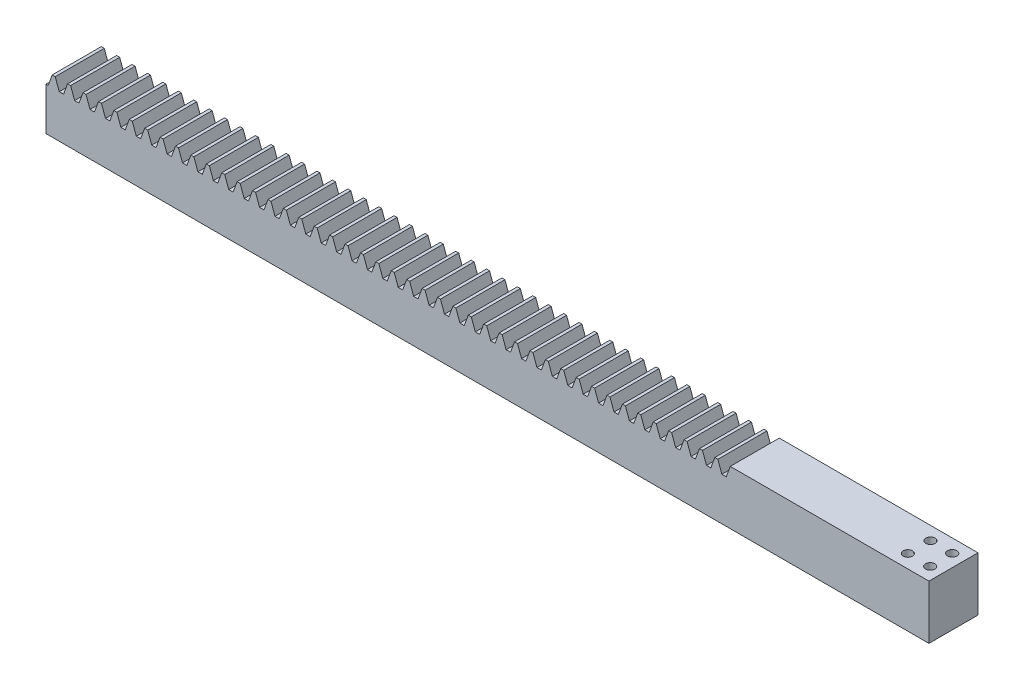
SolidWorks part; units mm, degrees
extrude "Blank" add sketch "BlankSke" against normal blind 10
sketch "BlankSke" plane through (0, 0, 0) normal (0, 0, 1) x (1, 0, 0)
  line L1 (0, 0) -> (140, 0)
  line L2 (0, 0) -> (0, 11)
  line L3 (0, 11) -> (140, 11)
  line L4 (140, 0) -> (140, 11)
  dimension "Length" = 140
ref_plane "Plane1" through (0, 0, 0) normal (0, 0, 1) x (1, 0, 0)
ref_plane "Plane2" through (0, 0, 0) normal (0, 1, 0) x (1, 0, 0)
ref_plane "Plane3" through (0, 0, 0) normal (1, 0, 0) x (0, 0, -1)
other "Configuration Table"
sketch "HoldingSke" plane through (0, 0, 0) normal (0, 1, 0) x (1, 0, 0)
  line L0 (0, 0) -> (0.1392, 0.9903)
  line L1 (-15, 0) -> (100, 0) construction
  line L2 (0, 0) -> (-2.1039, 2.3779)
  line L3 (0, 0) -> (-11.863, 4.5341)
  line L4 (0, 0) -> (5.9991, 6.2122)
  line L5 (0, 0) -> (-23.7986, -8.8762)
  line L6 (0, 0) -> (-10.5278, -7.1032)
  line L9 (-71.009, 38.7566) -> (60.548, 86.6394)
  line L10 (-76.2, 3.3779) -> (-66.2, 3.3779)
  line L11 (0, 0) -> (-10, 0)
  line L12 (-76.2, 101.6) -> (-76.162, 101.6)
  line L13 (24.9733, 27.94) -> (52.9518, 28.4284)
  line L14 (24.9733, 27.94) -> (24.9743, 27.94)
  line L15 (24.9733, 27.94) -> (100.4006, 29.5858)
  circle A0 centre (0, 0) radius 19.05
  circle A1 centre (0, 0) radius 5
  circle A2 centre (0, 0) radius 12.7
  dimension "Num_teeth" = 46
  dimension "Width" = 10
  dimension "Length" = 140
  dimension "Pitch_height" = 10
sketch "TooCutSkeIll" plane through (0, 0, 0) normal (0, 0, 1) x (1, 0, 0)
  line L0 (-1.2538, 10.9737) -> (-0.5045, 8.9152)
  line L1 (-0.2687, 8.75) -> (0.2687, 8.75)
  line L2 (0.5045, 8.9152) -> (1.2538, 10.9737)
  line L3 (140, 11) -> (0, 11) construction
  line L4 (0, 0) -> (0, 64.897) construction
  line L5 (-13.208, 10) -> (12.954, 10) construction
  line L6 (0, 0) -> (140, 0) construction
  line L7 (0.8994, 10) -> (0.8994, 48.7463) construction
  line L8 (-0.8994, 10) -> (-0.8994, 48.7463) construction
  line L9 (1.2914, 11) -> (1.2914, 11.0254)
  line L10 (-1.2914, 11) -> (-1.2914, 11.0254)
  line L11 (-1.2914, 11.0254) -> (1.2914, 11.0254)
  arc A0 (0.2687, 8.75) -> (0.5045, 8.9152) centre (0.2687, 9.001) ccw
  arc A1 (-0.5045, 8.9152) -> (-0.2687, 8.75) centre (-0.2687, 9.001) ccw
  arc A2 (1.2914, 11) -> (1.2538, 10.9737) centre (1.2914, 10.96) ccw
  arc A3 (-1.2538, 10.9737) -> (-1.2914, 11) centre (-1.2914, 10.96) ccw
  dimension "Addendum_plus" = 1.0254
  dimension "Pitch_height" = 10
  dimension "Pressure_angle" = 20
  dimension "Gap_width" = 1.7988
  dimension "Dedendum" = 1.25
extrude "ToothCutIll" [suppressed] cut sketch "TooCutSkeIll" against normal through all
sketch "TooCutSkeSim" plane through (0, 0, 0) normal (0, 0, 1) x (1, 0, 0)
  line L0 (0.4444, 8.75) -> (-0.4444, 8.75)
  line L1 (1.2726, 11.0254) -> (0.4444, 8.75)
  line L2 (0, 17.4625) -> (0, 53.467) construction
  line L3 (1.2726, 11.0254) -> (-1.2726, 11.0254)
  line L6 (-1.2726, 11.0254) -> (-0.4444, 8.75)
  line L9 (-0.8994, 10) -> (0.8994, 10) construction
  line L10 (0, 0) -> (140, 0) construction
  line L11 (0.8994, 10) -> (0.8994, 53.467) construction
  line L12 (-0.8994, 10) -> (-0.8994, 53.467) construction
  dimension "Addendum_plus" = 1.0254
  dimension "Pitch_height" = 10
  dimension "Pressure_angle" = 20
  dimension "Gap_width" = 1.7988
  dimension "Dedendum" = 1.25
extrude "ToothCutSim" cut sketch "TooCutSkeSim" against normal through all
pattern_linear "TeethCuts" count 46 spacing 3.1416 along (1, 0, 0) of "ToothCutIll", "ToothCutSim"
sketch "Sketch1" plane through (140, 0, 0) normal (1, 0, 0) x (0, 0, -1)
  line L4 (0, 11) -> (0, 0)
  line L5 (0, 0) -> (10, 0)
  line L6 (10, 0) -> (10, 11)
  line L7 (10, 11) -> (0, 11)
  line L8 (0, 11) -> (0, 0)
  line L9 (0, 0) -> (10, 0)
  line L10 (10, 0) -> (10, 11)
  line L11 (10, 11) -> (0, 11)
  dimension "D1" = 0
extrude "Boss-Extrude1" add sketch "Sketch1" along normal blind 40
sketch "Sketch3" plane through (0, 11, 0) normal (0, 1, 0) x (1, 0, 0)
  line L0 (180, 5) -> (158.3478, 5) construction
  line L1 (180, 10) -> (180, 0) construction
  line L2 (180, 0) -> (180, 5)
  circle A5 centre (177.53, 2.725) radius 0.95
  circle A6 centre (177.47, 7.275) radius 0.95
  circle A7 centre (173.03, 7.275) radius 0.95
  circle A8 centre (172.97, 2.725) radius 0.95
  point P5 (0, 0)
  point P7 (0, 0)
  point P16 (0, 0)
  dimension "D1" = 1.9
  dimension "D4" = 2.275
  dimension "D7" = 1.9
  dimension "D9" = 1.9
  dimension "D3" = 1.9
  dimension "D2" = 4.55
  dimension "D8" = 4.44
  dimension "D10" = 4.56
extrude "Cut-Extrude1" cut sketch "Sketch3" against normal through all contours A7 | A6 | A5 | A8
equation "' \"Module@HoldingSke\" = 6.35"
equation "' \"Num_teeth@HoldingSke\" = 12"
equation "' \"Ap@HoldingSke\" =  20"
equation "' \"Ap@HoldingSke\" = 20"
equation "' \"Width@HoldingSke\" = 0.25 * 25.4"
equation "' \"Show_teeth@HoldingSke\" = 500"
equation "' \"Backlash@HoldingSke\" = 0.009 * 25.4"
equation "' \"Addendum_fac@HoldingSke\" = 1.0"
equation "' \"Dedendum_fac@HoldingSke\" = 1.25"
equation "' \"Dedendum_add@HoldingSke\" = 0.00005 * 25.4"
equation "' \"Clearance_fac@HoldingSke\" = 0.25"
equation "' \"Pitch_height@HoldingSke\" = 1 * 25.4"
equation "' \"Length@HoldingSke\" = 4.71 * 25.4"
equation "\"Pitch@HoldingSke\" = 1 / \"Module@HoldingSke\""
equation "\"MPH@HoldingSke\" = \"Dedendum_fac@HoldingSke\" / \"Pitch@HoldingSke\" + 2 * \"Dedendum_add@HoldingSke\" + 0.002 * 25.4"
equation "\"MPH@HoldingSke\" = ((sgn( \"MPH@HoldingSke\" - \"Pitch_height@HoldingSke\")+1)*( \"MPH@HoldingSke\" - \"Pitch_height@HoldingSke\"))/2 + \"Pitch_height@HoldingSke\""
equation "\"Blank_height@BlankSke\" = \"Pitch_height@HoldingSke\" + \"Addendum_fac@HoldingSke\"  / \"Pitch@HoldingSke\" "
equation "\"Length@BlankSke\" =  \"Length@HoldingSke\""
equation "\"Face_width@Blank\" = \"Width@HoldingSke\""
equation "\"Pressure_angle@TooCutSkeIll\" = \"Ap@HoldingSke\""
equation "\"Addendum_plus@TooCutSkeIll\" =  \"Addendum_fac@HoldingSke\"  / \"Pitch@HoldingSke\" + 0.001 *25.4"
equation "\"Dedendum@TooCutSkeIll\" = \"Dedendum_fac@HoldingSke\"  / \"Pitch@HoldingSke\""
equation "\"Pitch_height@TooCutSkeIll\" =  \"MPH@HoldingSke\""
equation "\"Gap_width@TooCutSkeIll\" = 3.14159265 / 2 / \"Pitch@HoldingSke\" + 6 * \"Backlash@HoldingSke\""
equation "\"Pressure_angle@TooCutSkeSim\" = \"Ap@HoldingSke\""
equation "\"Addendum_plus@TooCutSkeSim\" =  \"Addendum_fac@HoldingSke\"  / \"Pitch@HoldingSke\" + 0.001 * 25.4"
equation "\"Dedendum@TooCutSkeSim\" = \"Dedendum_fac@HoldingSke\"  / \"Pitch@HoldingSke\""
equation "\"Pitch_height@TooCutSkeSim\" =  \"MPH@HoldingSke\""
equation "\"Gap_width@TooCutSkeSim\" = 3.14159265 / 2 / \"Pitch@HoldingSke\" + 6 * \"Backlash@HoldingSke\""
equation "\"Root_fillet@TooCutSkeIll\" = \"Clearance_fac@HoldingSke\" / \"Pitch@HoldingSke\" + \"Dedendum_add@HoldingSke\""
equation "\"Break_rad@TooCutSkeIll\" = 0.02 / \"Pitch@HoldingSke\" * 2"
equation "\"Linear_pitch@TeethCuts\" = 3.14159265 / \"Pitch@HoldingSke\""
equation "\"Num_teeth@HoldingSke\" = int( ( \"Length@HoldingSke\" + 0 ) / (3.14159265 / \"Pitch@HoldingSke\")) + 0.9999  + 1"
equation " \"Num_teeth@TeethCuts\" = int( \"Show_teeth@HoldingSke\" ) + 1"
equation " \"Num_teeth@TeethCuts\" = ((sgn( \"Num_teeth@TeethCuts\" - \"Num_teeth@HoldingSke\" )-1)*( \"Num_teeth@TeethCuts\" - \"Num_teeth@HoldingSke\" ))/-2+ \"Num_teeth@HoldingSke\""
equation " \"Num_teeth@TeethCuts\" = ((sgn( \"Num_teeth@TeethCuts\" - 2.0)+1)*( \"Num_teeth@TeethCuts\" - 2.0))/2 +2.0"
